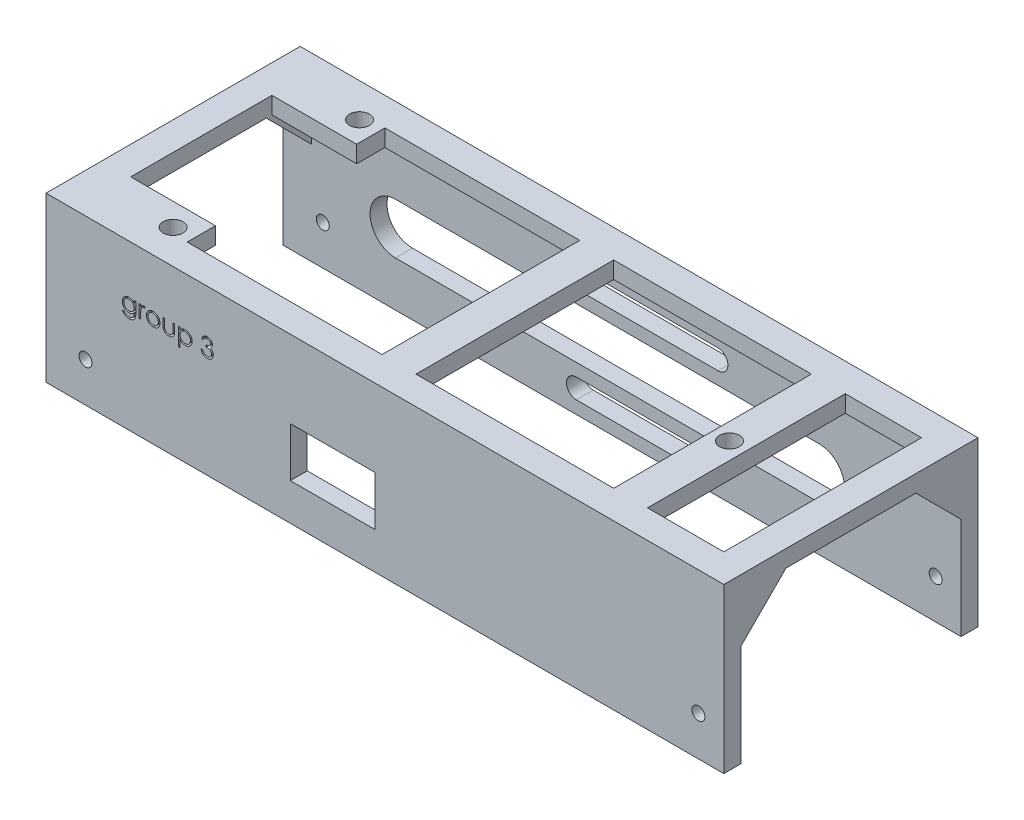
SolidWorks part; units mm, degrees
other "Markup1"
sketch "Sketch23" plane through (120, 29, 45) normal (0.0467, 0.9512, 0.3049) x (0.9885, 0, -0.1514)
ref_plane "Front Plane" through (0, 0, 0) normal (0, 0, 1) x (1, 0, 0)
ref_plane "Top Plane" through (0, 0, 0) normal (0, 1, 0) x (1, 0, 0)
ref_plane "Right Plane" through (0, 0, 0) normal (1, 0, 0) x (0, 0, -1)
sketch "Sketch1" plane through (0, 0, 0) normal (0, 0, 1) x (1, 0, 0)
  line L9 (21.172, -17.9478) -> (91.172, -17.9478)
  line L10 (21.172, -17.9478) -> (21.172, -40.3878)
  line L11 (4, -8) -> (200.227, -8) construction
  line L12 (4, -8) -> (-67.5185, -8) construction
  line L13 (21.172, -40.3878) -> (91.172, -40.3878)
  line L14 (91.172, -17.9478) -> (91.172, -40.3878)
  line L15 (0, 0) -> (120, 0)
  line L16 (0, 0) -> (0, 29)
  line L17 (0, 29) -> (120, 29)
  line L18 (120, 0) -> (120, 29)
  circle A0 centre (4, 7) radius 1.15
  circle A1 centre (4, 7) radius 15 construction
  circle A3 centre (77.172, -29.1678) radius 3.6067
  circle A4 centre (116, 7) radius 15 construction
  circle A5 centre (116, 7) radius 1.15
  point P19 (21.172, -29.1678)
  dimension "D4" = 30
  dimension "D2" = 14
  dimension "D7" = 30
  dimension "D11" = 4
  dimension "D13" = 2.3
  dimension "D14" = 2.3
  dimension "D3" = 70
  dimension "D5" = 22.44
  dimension "D6" = 120
  dimension "D8" = 29
  dimension "D9" = 4
  dimension "D10" = 7
  dimension "D12" = 7
extrude "Boss-Extrude5" add sketch "Sketch1" along normal blind 45 contours L16 L15 L18 L17
shell "Shell9" thickness 3 removed face at (120, 14.5, 22.5) removed face at (60, 0, 22.5) removed face at (0, 14.5, 22.5)
sketch "Sketch3" plane through (0, 0, 0) normal (0, 0, -1) x (-1, 0, 0)
  line L0 (0, 0) -> (-120, 0) construction
  line L1 (-120, 0) -> (-120, 29) construction
  line L2 (0, 0) -> (0, 29) construction
  circle A0 centre (-7, 7) radius 1.15
  circle A1 centre (-115.5, 7) radius 1.15
  dimension "D1" = 2.3
  dimension "D2" = 2.3
  dimension "D3" = 7
  dimension "D4" = 4.5
  dimension "D5" = 7
  dimension "D6" = 7
extrude "Cut-Extrude2" cut sketch "Sketch3" against normal blind 79
sketch "Sketch6" plane through (0, 0, 0) normal (0, 0, -1) x (-1, 0, 0)
  line L0 (-76.9735, 21) -> (-51.8835, 21) construction
  line L1 (-76.9735, 22.75) -> (-51.8835, 22.75)
  line L2 (-76.9735, 19.25) -> (-51.8835, 19.25)
  line L7 (41.5249, -18.7743) -> (41.5249, -41.2143) construction
  line L8 (-94.8735, 12.5) -> (-19.8735, 12.5) construction
  line L9 (-94.8735, 17) -> (-19.8735, 17)
  line L10 (-94.8735, 8) -> (-19.8735, 8)
  line L11 (-19.8735, 12.5) -> (-17.326, 12.5) construction
  line L12 (-76.9735, 4) -> (-51.8835, 4) construction
  line L13 (-76.9735, 2.25) -> (-51.8835, 2.25)
  line L14 (-76.9735, 5.75) -> (-51.8835, 5.75)
  line L15 (4.7849, -29.9943) -> (74.7849, -29.9943) construction
  line L20 (4.7849, -18.7743) -> (74.7849, -18.7743)
  line L21 (4.7849, -18.7743) -> (4.7849, -41.2143)
  line L22 (4.7849, -41.2143) -> (74.7849, -41.2143)
  line L23 (74.7849, -18.7743) -> (74.7849, -41.2143)
  line L24 (-120, 0) -> (-120, 29) construction
  line L25 (63.3749, -18.7743) -> (63.3749, -41.2143) construction
  line L26 (0, 29) -> (-120, 29) construction
  arc A4 (-94.8735, 17) -> (-94.8735, 8) centre (-94.8735, 12.5) ccw
  arc A5 (-76.9735, 22.75) -> (-76.9735, 19.25) centre (-76.9735, 21) ccw
  arc A6 (-51.8835, 19.25) -> (-51.8835, 22.75) centre (-51.8835, 21) ccw
  arc A7 (-19.8735, 8) -> (-19.8735, 17) centre (-19.8735, 12.5) ccw
  arc A8 (-76.9735, 2.25) -> (-76.9735, 5.75) centre (-76.9735, 4) cw
  arc A9 (-51.8835, 5.75) -> (-51.8835, 2.25) centre (-51.8835, 4) cw
  circle A15 centre (16.1349, -29.9943) radius 1.5
  circle A16 centre (36.3249, -21.4943) radius 1.5
  circle A17 centre (36.3249, -38.4943) radius 1.5
  circle A18 centre (36.3249, -38.4943) radius 1.5
  circle A19 centre (27.0349, -29.9943) radius 2.3201
  point P11 (-64.4285, 21)
  point P19 (-57.3735, 12.5)
  point P31 (-64.4285, 4)
  dimension "D8" = 1.75
  dimension "D13" = 4.5
  dimension "D10" = 3
  dimension "D14" = 3
  dimension "D9" = 25.09
  dimension "D2" = 8.5
  dimension "D3" = 17.9
  dimension "D4" = 70
  dimension "D5" = 22.44
  dimension "D6" = 36.74
  dimension "D7" = 11.35
  dimension "D11" = 5.2
  dimension "D12" = 8.5
  dimension "D15" = 22.25
  dimension "D16" = 75
  dimension "D17" = 25.1265
  dimension "D18" = 11.41
  dimension "D19" = 16.5
extrude "Cut-Extrude8" cut sketch "Sketch6" against normal blind 23 contours L10 A7 L9 | L2 A6 L1 A5 | L13 A9 L14 A8 region at (64.4285, 21, 0) region at (57.3735, 12.5, 0)
sketch "Sketch7" plane through (0, 0, 45) normal (0, 0, 1) x (1, 0, 0)
  line L1 (43.2462, 15.2962) -> (58.2462, 15.2962)
  line L2 (43.2462, 15.2962) -> (43.2462, 6.5462)
  line L3 (43.2462, 6.5462) -> (58.2462, 6.5462)
  line L4 (58.2462, 15.2962) -> (58.2462, 6.5462)
  line L5 (0, 0) -> (120, 0) construction
  line L7 (0, 0) -> (0, 29) construction
  dimension "D1" = 43.2462
  dimension "D2" = 15
  dimension "D3" = 8.75
  dimension "D4" = 15.2962
extrude "Cut-Extrude9" cut sketch "Sketch7" against normal blind 20
sketch "Sketch13" plane through (0, 29, 0) normal (0, 1, 0) x (1, 0, 0)
  line L1 (0, 0) -> (120, 0) construction
  line L4 (5, -5) -> (115, -5)
  line L5 (5, -5) -> (5, -40)
  line L6 (5, -40) -> (115, -40)
  line L8 (0, -45) -> (0, 0) construction
  line L16 (115, -5) -> (115, -40)
  line L17 (120, -45) -> (120, 0) construction
  point P0 (128.3255, -21.347)
  dimension "D1" = 5
  dimension "D2" = 5
  dimension "D5" = 5
  dimension "D6" = 35
extrude "Cut-Extrude14" cut sketch "Sketch13" against normal blind 10
sketch "Sketch17" plane through (0, 29, 0) normal (0, 1, 0) x (1, 0, 0)
  line L0 (0, -22.5) -> (120, -22.5) construction
  line L1 (5, -5) -> (20, -5)
  line L2 (5, -5) -> (5, -10)
  line L3 (5, -10) -> (20, -10)
  line L4 (20, -5) -> (20, -10)
  line L5 (5, -40) -> (20, -40)
  line L6 (5, -40) -> (5, -35)
  line L7 (5, -35) -> (20, -35)
  line L8 (20, -40) -> (20, -35)
  line L17 (0, -45) -> (0, 0) construction
  line L18 (120, -45) -> (120, 0) construction
  line L25 (115, -5) -> (5, -5) construction
  line L26 (95.5, -5) -> (101.5, -5)
  line L27 (95.5, -5) -> (95.5, -40)
  line L28 (95.5, -40) -> (101.5, -40)
  line L29 (101.5, -5) -> (101.5, -40)
  line L30 (5, -40) -> (115, -40) construction
  line L32 (54.5, -5) -> (60.5, -5)
  line L33 (54.5, -5) -> (54.5, -40)
  line L34 (54.5, -40) -> (60.5, -40)
  line L35 (60.5, -5) -> (60.5, -40)
  circle A0 centre (16.5, -39) radius 1.75
  circle A1 centre (16.5, -6) radius 1.75
  circle A2 centre (98.5, -22.5) radius 1.75
  point P36 (0, 0)
  point P37 (98.0553, -22.5)
  point P38 (0, 0)
  point P39 (0, 0)
  point P40 (97.2763, -22.5)
  point P41 (98.5, -5)
  line M10 (5, -40) -> (5, -5)
  line M11 (5, -5) -> (115, -5)
  line M13 (115, -40) -> (5, -40)
  dimension "D3" = 3.5
  dimension "D6" = 3.5
  dimension "D11" = 33
  dimension "D12" = 16.5
  dimension "D13" = 3.5
  dimension "D1" = 5
  dimension "D2" = 15
  dimension "D4" = 5
  dimension "D5" = 15
  dimension "D7" = 6
  dimension "D8" = 18.5
  dimension "D9" = 6
  dimension "D10" = 35
extrude "Boss-Extrude6" add sketch "Sketch17" against normal blind 3 contours A1 L3 L4 M11 M10 | L1 A1 | A0 L8 L7 M13 M10 | L5 A0 | L33 L32 L35 L34 | L27 L26 L29 L28 region at (12.0151, 29, 7.6523) region at (16.5, 29, 6.2435) region at (12.0151, 29, 37.3477) region at (16.5, 29, 38.7565)
extrude "Cut-Extrude16" cut sketch "Sketch17<4>" against normal blind 10 contours A2 L0 | L0 A2 | L1 A1 | L1 A1 | L5 A0 | L5 A0 | A2 region at (98.5, 29, 21.7573) region at (98.5, 29, 23.2427) region at (16.5, 29, 4.6937) region at (16.5, 29, 6.2435) region at (16.5, 29, 38.7565) region at (16.5, 29, 40.3063)
sketch "Sketch17<4>" plane through (0, 29, 0) normal (0, 1, 0) x (1, 0, 0) same geometry as "Sketch17"
sketch "Sketch20" plane through (0, 0, 45) normal (0, 0, 1) x (1, 0, 0)
  line L0 (13.2558, 18.0126) -> (38.9246, 18.0126) construction
  text T0 "group 3"
extrude "Cut-Extrude15" cut sketch "Sketch20" against normal blind 1.5
sketch "Sketch21" plane through (0, 0, 0) normal (-1, 0, 0) x (0, 0, 1)
  line L0 (3, 26) -> (3, 18)
  line L1 (3, 0) -> (3, 26) construction
  line L2 (3, 18) -> (11, 26)
  line L3 (42, 26) -> (3, 26) construction
  line L4 (11, 26) -> (3, 26)
  line L5 (42, 26) -> (34, 26)
  line L6 (34, 26) -> (42, 18)
  line L7 (42, 0) -> (42, 26) construction
  line L8 (42, 18) -> (42, 26)
  dimension "D1" = 8
  dimension "D2" = 8
  dimension "D3" = 8
  dimension "D4" = 8
extrude "Boss-Extrude7" add sketch "Sketch21" against normal blind 5
sketch "Sketch22" plane through (120, 0, 0) normal (1, 0, 0) x (0, 0, -1)
  line L0 (-42, 26) -> (-42, 18)
  line L1 (-42, 18) -> (-34, 26)
  line L2 (-34, 26) -> (-42, 26)
  line L3 (-11, 26) -> (-3, 26)
  line L4 (-3, 26) -> (-3, 18)
  line L5 (-3, 18) -> (-11, 26)
extrude "Boss-Extrude8" add sketch "Sketch22" against normal blind 5
equation "\"slot­_width\"=25.09"
equation "\"D9@Sketch6\"=\"slot­_width\""
